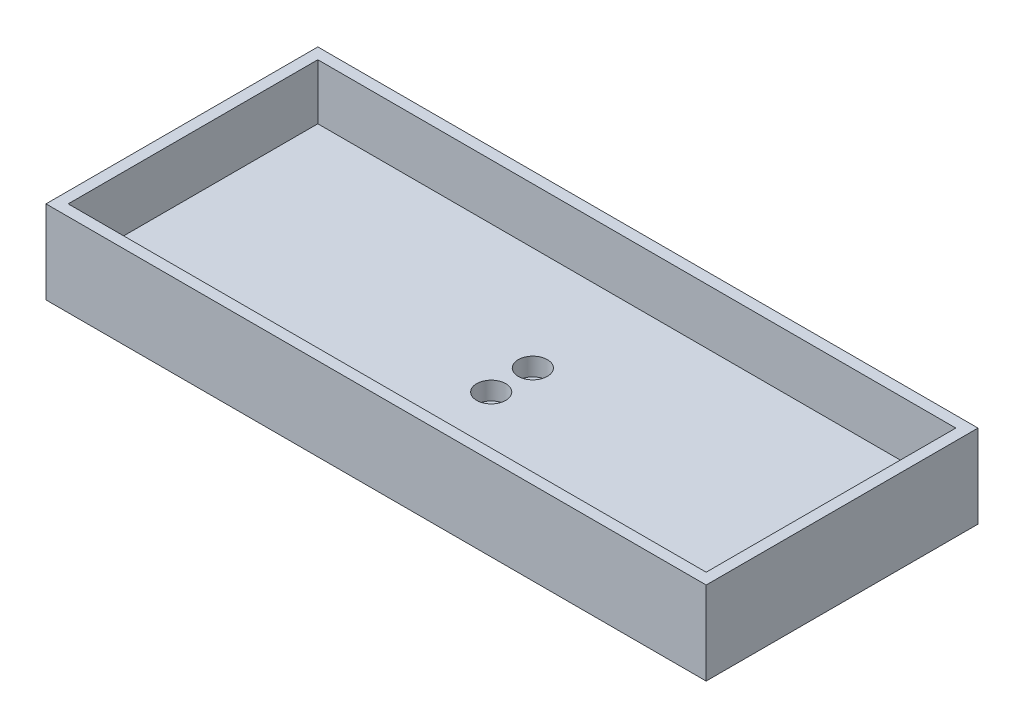
SolidWorks part; units mm, degrees
ref_plane "Front Plane" through (0, 0, 0) normal (0, 0, 1) x (1, 0, 0)
ref_plane "Top Plane" through (0, 0, 0) normal (0, 1, 0) x (1, 0, 0)
ref_plane "Right Plane" through (0, 0, 0) normal (1, 0, 0) x (0, 0, -1)
sketch "Sketch1" plane through (0, 0, 0) normal (0, 1, 0) x (1, 0, 0)
  line L0 (-119, 49) -> (119, 49)
  line L1 (-115, 45) -> (115, 45)
  line L2 (-115, 45) -> (-115, -45)
  line L3 (-115, -45) -> (115, -45)
  line L4 (115, 45) -> (115, -45)
  line L5 (119, 49) -> (119, -49)
  line L6 (-119, -49) -> (119, -49)
  line L7 (-119, 49) -> (-119, -49)
  point P4 (0, 45)
  point P6 (-115, 0)
  dimension "D2" = 90
  dimension "D3" = 230
  dimension "D1" = 4
extrude "Boss-Extrude1" add sketch "Sketch1" along normal blind 30
extrude "Boss-Extrude2" add sketch "Sketch1<2>" along normal blind 10 separate body contours L1 L4 L3 L2
sketch "Sketch1<2>" plane through (0, 0, 0) normal (0, 1, 0) x (1, 0, 0) same geometry as "Sketch1"
sketch "Sketch3" plane through (0, 10, 0) normal (0, 1, 0) x (1, 0, 0)
  line L0 (0, 45) -> (0, -45) construction
  line L1 (115, 45) -> (-115, 45) construction
  line L2 (-115, -45) -> (115, -45) construction
  line L3 (-115, 0) -> (115, 0) construction
  line L4 (-115, 45) -> (-115, -45) construction
  line L5 (115, 45) -> (115, -45) construction
  circle A0 centre (0, 7.5) radius 3.2
  circle A1 centre (0, 7.5) radius 5.25
  circle A2 centre (0, -7.5) radius 3.2
  circle A3 centre (0, -7.5) radius 5.25
  dimension "D1" = 6.4
  dimension "D2" = 10.5
  dimension "D3" = 15
extrude "Cut-Extrude1" cut sketch "Sketch3" against normal through all contours A0 | A2
extrude "Cut-Extrude2" cut sketch "Sketch3<3>" against normal blind 6.5 contours A1 | A3
sketch "Sketch3<3>" plane through (0, 10, 0) normal (0, 1, 0) x (1, 0, 0) same geometry as "Sketch3"
